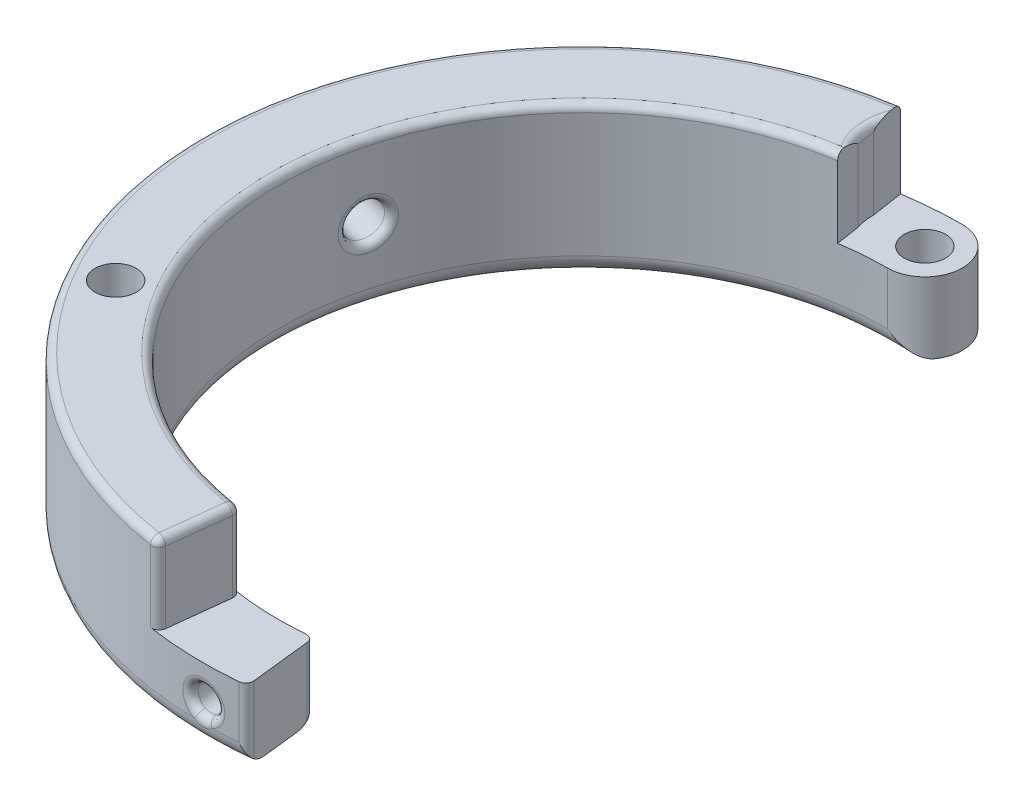
SolidWorks part; units mm, degrees
ref_plane "Front Plane" through (0, 0, 0) normal (0, 0, 1) x (1, 0, 0)
ref_plane "Top Plane" through (0, 0, 0) normal (0, 1, 0) x (1, 0, 0)
ref_plane "Right Plane" through (0, 0, 0) normal (1, 0, 0) x (0, 0, -1)
sketch "Sketch1" plane through (0, 0, 0) normal (0, 1, 0) x (1, 0, 0)
  line L0 (0, 50.5) -> (29.9823, 50.5) construction
  line L1 (0, 0) -> (0, 45.5) construction
  line L2 (0, 0) -> (-39.4042, -22.75) construction
  line L3 (4.5591, -41.2367) -> (5.4385, -49.1902)
  line L4 (0, 0) -> (4.4505, -40.2547) construction
  circle A0 centre (0, 45.5) radius 2.75
  arc A1 (0, 50.5) -> (0, 40.5) centre (0, 45.5) cw
  arc A2 (0, 50.5) -> (0, -50.5) centre (0, 0) ccw
  arc A3 (0, 40.5) -> (0, -40.5) centre (0, 0) ccw
  arc A4 (0, -40.5) -> (0, -50.5) centre (0, -45.5) cw construction
  circle A5 centre (-39.4042, -22.75) radius 2.75
  arc A6 (0, -40.5) -> (3.4793, -40.3503) centre (0, 0) ccw
  arc A7 (0, -50.5) -> (4.5343, -50.296) centre (0, 0) ccw
  arc A8 (4.5343, -50.296) -> (5.4385, -49.1902) centre (4.4445, -49.3001) ccw
  arc A9 (3.4793, -40.3503) -> (4.5591, -41.2367) centre (3.5652, -41.3466) cw
  dimension "D1" = 5.5
  dimension "D7" = 1
  dimension "D2" = 10
  dimension "D3" = 40.5
  dimension "D5" = 120
  dimension "D6" = 45.5
  dimension "D4" = 2
extrude "Boss-Extrude1" add sketch "Sketch1" along normal blind 20
sketch "Sketch3" plane through (0, 0, 0) normal (0, 0, 1) x (1, 0, 0)
  line L0 (4.5343, 20) -> (-50.5, 20) construction
  circle A0 centre (0, 15) radius 1.75
  circle A1 centre (0, 5) radius 1.75
  dimension "D1" = 3.5
  dimension "D4" = 3.5
  dimension "D2" = 5
  dimension "D3" = 5
extrude "Cut-Extrude2" cut sketch "Sketch3" along normal blind 71
sketch "Sketch2" plane through (0, 20, 0) normal (0, 1, 0) x (1, 0, 0)
  line L0 (0, -1000) -> (0, 49000) construction
  line L1 (5.4385, -49.1902) -> (4.5591, -41.2367)
  line L2 (5.4385, -49.1902) -> (4.5591, -41.2367) construction
  line L3 (-5.4385, -49.1902) -> (-4.5591, -41.2367) construction
  line L4 (-4.4505, -40.2547) -> (0, 0) construction
  line L5 (0, 0) -> (-5.5107, 35.9551) construction
  line L6 (0, 45.5) -> (-4.3301, 48) construction
  line L7 (0, 45.5) -> (-39.4042, -22.75) construction
  line L10 (-4.3301, 48) -> (-6.2137, 49.0875) construction
  line L11 (-6.1357, 40.0325) -> (-6.629, 43.2514) construction
  line L12 (-6.1357, 40.0325) -> (-6.629, 43.2514)
  line L13 (-5.5107, 35.9551) -> (-6.1357, 40.0325) construction
  line L17 (-6.9982, 45.66) -> (-7.6507, 49.9171)
  line L18 (-5.4193, -40.1358) -> (-6.5623, -50.0718)
  arc A0 (0, 50.5) -> (0, 40.5) centre (0, 45.5) ccw construction
  arc A1 (-6.9982, 45.66) -> (-6.629, 43.2514) centre (0, 45.5) ccw
  arc A2 (0, 52.5) -> (0, 38.5) centre (0, 45.5) ccw construction
  arc A3 (0, 40.5) -> (-4.6144, 40.2363) centre (0, 0) ccw construction
  arc A5 (0, 50.5) -> (4.5343, -50.296) centre (0, 0) ccw
  arc A6 (4.5343, -50.296) -> (5.4385, -49.1902) centre (4.4445, -49.3001) ccw
  arc A7 (4.5591, -41.2367) -> (3.4793, -40.3503) centre (3.5652, -41.3466) ccw
  arc A8 (0, 40.5) -> (3.4793, -40.3503) centre (0, 0) ccw
  arc A9 (0, 40.5) -> (0, 50.5) centre (0, 45.5) ccw
  arc A10 (-7.6507, 49.9171) -> (-6.5623, -50.0718) centre (0, 0) ccw construction
  arc A11 (4.5343, -50.296) -> (5.4385, -49.1902) centre (4.4445, -49.3001) ccw construction
  arc A12 (4.5591, -41.2367) -> (3.4793, -40.3503) centre (3.5652, -41.3466) ccw construction
  arc A13 (-6.4367, 39.9852) -> (-5.4193, -40.1358) centre (0, 0) ccw construction
  arc A16 (-4.4505, -40.2547) -> (0, -40.5) centre (0, 0) ccw construction
  arc A17 (0, -40.5) -> (3.4793, -40.3503) centre (0, 0) ccw construction
  arc A18 (0, -50.5) -> (4.5343, -50.296) centre (0, 0) ccw construction
  arc A19 (-5.5495, -50.1942) -> (0, -50.5) centre (0, 0) ccw construction
  arc A20 (-5.4385, -49.1902) -> (-6.5623, -50.0718) centre (-6.4324, -49.0803) cw construction
  arc A21 (-4.5591, -41.2367) -> (-5.4193, -40.1358) centre (-5.5531, -41.1268) ccw construction
  arc A22 (0, 50.5) -> (-6.5623, -50.0718) centre (0, 0) cw
  arc A23 (-5.4193, -40.1358) -> (-6.1357, 40.0325) centre (0, 0) ccw
  arc A24 (0, 50.5) -> (4.5343, -50.296) centre (0, 0) ccw construction
  arc A25 (-6.3062, 48.5385) -> (-6.9982, 45.66) centre (0, 45.5) ccw construction
  circle M14 centre (0, 45.5) radius 2.75
  arc M15 (0, 50.5) -> (4.5343, -50.296) centre (0, 0) ccw
  arc M16 (4.5343, -50.296) -> (5.4385, -49.1902) centre (4.4445, -49.3001) ccw
  line M17 (5.4385, -49.1902) -> (4.5591, -41.2367)
  arc M18 (4.5591, -41.2367) -> (3.4793, -40.3503) centre (3.5652, -41.3466) ccw
  arc M19 (3.4793, -40.3503) -> (0, 40.5) centre (0, 0) cw
  arc M20 (0, 40.5) -> (0, 50.5) centre (0, 45.5) ccw
  dimension "D4" = 1
  dimension "D1" = 0
  dimension "D2" = 2
extrude "Cut-Extrude1" cut sketch "Sketch2" against normal blind 10.5 contours L18 M19 M15 M16 M17 M18 | A23 A22 M18 M17 M16 M20 | L17 A1 L12 M19 M20 M15 M14 region at (-0.5189, 20, 45.5563) region at (6.1193, 20, 45.0895) region at (4.8358, 20, -45.5)
sketch "Sketch4" plane through (0, 0, 0) normal (0, -1, 0) x (1, 0, 0)
  circle A0 centre (0, -45.5) radius 2.75 construction
  circle A1 centre (-39.4042, 22.75) radius 2.75 construction
  circle A2 centre (0, -45.5) radius 2.75
  circle A3 centre (-39.4042, 22.75) radius 2.75
extrude "Boss-Extrude2" add sketch "Sketch4" against normal blind 3
fillet "Fillet1" radius 2.5 2 edges at (-50.449, 0, 2.2694) (-40.4626, 0, 1.7412) tangent propagation no
fillet "Fillet2" radius 1 6 edges at (-6.9192, 20, -44.4395) (-5.4193, 14.75, 40.1358) (-6.5623, 14.75, 50.0718) (-40.4984, 20, 0.3619) (-5.9908, 20, 45.1038) (-50.497, 20, 0.5496)
ref_plane "Plane1" through (-39.12, 0, -10.4822) normal (0.9659, 0, 0.2588) x (0, -1, 0)
sketch "Sketch5" plane through (-41.0271, 0, -3.3646) normal (0.9659, 0, 0.2588) x (0.2588, 0, -0.9659)
  circle A0 centre (7.3686, 10) radius 2.35
  point P2 (0, 0)
  dimension "D2" = 4.7
  dimension "D1" = 10
extrude "Cut-Extrude3" cut sketch "Sketch5" against normal through all both and the other way through all
fillet "Fillet3" radius 1 4 edges at (-49.3213, 9.4623, -10.8472) (-39.6497, 10.5361, -8.2554) (1.7034, 5.4013, 50.4713) (1.7035, 4.5993, 40.4642)
